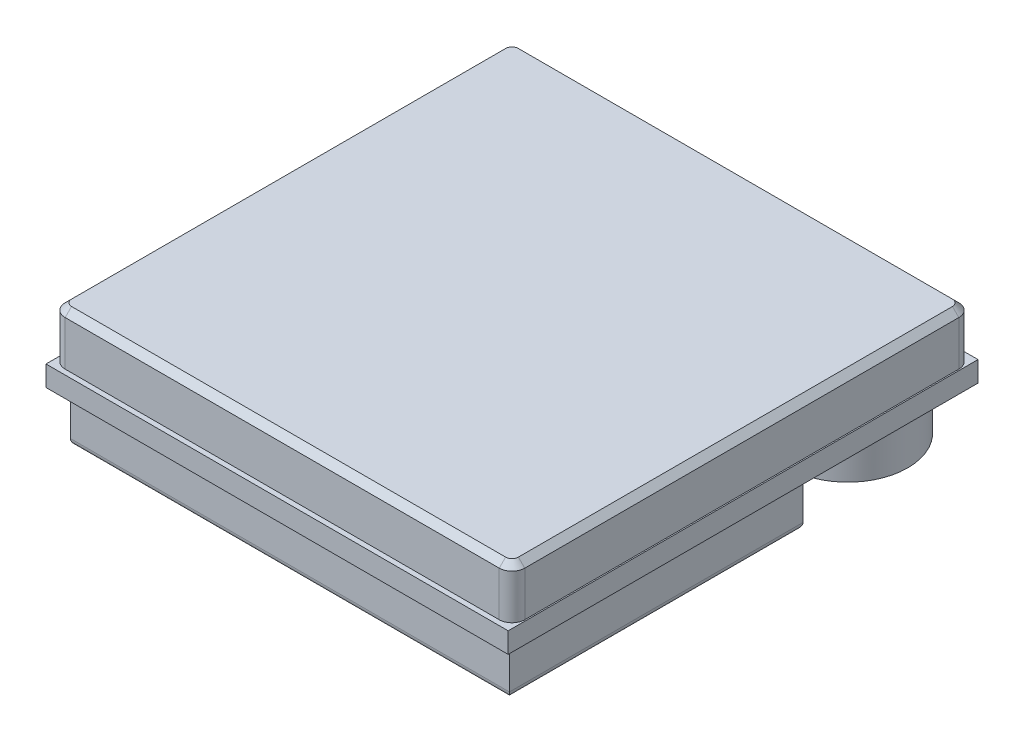
SolidWorks part; units mm, degrees
ref_plane "Front Plane" through (0, 0, 0) normal (0, 0, 1) x (1, 0, 0)
ref_plane "Top Plane" through (0, 0, 0) normal (0, 1, 0) x (1, 0, 0)
ref_plane "Right Plane" through (0, 0, 0) normal (1, 0, 0) x (0, 0, -1)
sketch "Sketch1" plane through (0, 0, 0) normal (0, 1, 0) x (1, 0, 0)
  line L1 (-9.05, 9.2) -> (9.05, 9.2)
  line L2 (-9.05, 9.2) -> (-9.05, -9.2)
  line L3 (-9.05, -9.2) -> (9.05, -9.2)
  line L4 (9.05, 9.2) -> (9.05, -9.2)
  line L5 (-9.05, 9.2) -> (9.05, -9.2) construction
  line L6 (-9.05, -9.2) -> (9.05, 9.2) construction
  point P0 (0, 0)
  dimension "D1" = 18.4
  dimension "D2" = 18.1
extrude "Boss-Extrude1" add sketch "Sketch1" along normal mid plane 0.8
sketch "Sketch2" plane through (0, 0.4, 0) normal (0, 1, 0) x (1, 0, 0)
  line L1 (9, 9) -> (-9, 9)
  line L2 (9, 9) -> (9, -9)
  line L3 (9, -9) -> (-9, -9)
  line L4 (-9, 9) -> (-9, -9)
  line L5 (9, 9) -> (-9, -9) construction
  line L6 (9, -9) -> (-9, 9) construction
  point P0 (0, 0)
  dimension "D1" = 18
extrude "Boss-Extrude2" add sketch "Sketch2" along normal blind 2
sketch "Sketch3" plane through (0, -0.4, 0) normal (0, -1, 0) x (1, 0, 0)
  line L0 (0, 9.2) -> (0, -9.2) construction
  line L1 (-9.05, 9.2) -> (9.05, 9.2) construction
  line L2 (9.05, -9.2) -> (-9.05, -9.2) construction
  line L4 (-3.075, -4.4) -> (3.075, -4.4)
  line L5 (-3.075, -4.4) -> (-3.075, -8.7)
  line L6 (-3.075, -8.7) -> (3.075, -8.7)
  line L7 (3.075, -4.4) -> (3.075, -8.7)
  line L8 (-3.075, -4.4) -> (3.075, -8.7) construction
  line L9 (-3.075, -8.7) -> (3.075, -4.4) construction
  point P6 (0, -6.55)
  dimension "D1" = 6.15
  dimension "D2" = 4.3
  dimension "D3" = 0.5
extrude "Boss-Extrude3" add sketch "Sketch3" along normal blind 3
sketch "Sketch4" plane through (0, 0, -8.7) normal (0, 0, -1) x (-1, 0, 0)
  line L8 (2.575, -0.9) -> (-2.575, -0.9)
  line L9 (-2.575, -0.9) -> (-2.575, -2.9)
  line L10 (-2.575, -2.9) -> (2.575, -2.9)
  line L11 (2.575, -2.9) -> (2.575, -0.9)
  line L12 (2.575, -0.9) -> (-2.575, -0.9)
  line L13 (-2.575, -0.9) -> (-2.575, -2.9)
  line L14 (-2.575, -2.9) -> (2.575, -2.9)
  line L15 (2.575, -2.9) -> (2.575, -0.9)
  dimension "D1" = 0.5
extrude "Cut-Extrude1" cut sketch "Sketch4" against normal blind 3.5
sketch "Sketch5" plane through (0, -0.4, 0) normal (0, -1, 0) x (1, 0, 0)
  line L0 (0, 9.2) -> (0, -9.2) construction
  line L1 (-9.05, 9.2) -> (9.05, 9.2) construction
  line L2 (9.05, -9.2) -> (-9.05, -9.2) construction
  line L4 (-8.6, 8.7) -> (8.6, 8.7)
  line L5 (-8.6, 8.7) -> (-8.6, -2.8)
  line L6 (-8.6, -2.8) -> (8.6, -2.8)
  line L7 (8.6, 8.7) -> (8.6, -2.8)
  line L8 (-8.6, 8.7) -> (8.6, -2.8) construction
  line L9 (-8.6, -2.8) -> (8.6, 8.7) construction
  point P6 (0, 2.95)
  dimension "D1" = 0.5
  dimension "D2" = 17.2
  dimension "D3" = 11.5
extrude "Boss-Extrude4" add sketch "Sketch5" along normal blind 2
fillet "Fillet1" radius 0.25 4 edges at (0, -2.4, -2.8) (-8.6, -2.4, 2.95) (0, -2.4, 8.7) (8.6, -2.4, 2.95)
sketch "Sketch6" plane through (0, -0.4, 0) normal (0, -1, 0) x (1, 0, 0)
  line L9 (8.85, -9) -> (8.85, 9)
  line L10 (8.85, 9) -> (-8.85, 9)
  line L11 (-8.85, 9) -> (-8.85, -9)
  line L12 (-8.85, -9) -> (8.85, -9)
  line L13 (8.85, -9) -> (8.85, 9)
  line L14 (8.85, 9) -> (-8.85, 9)
  line L15 (-8.85, 9) -> (-8.85, -9)
  line L16 (-8.85, -9) -> (8.85, -9)
  circle A0 centre (6.5, -6.65) radius 2.35
  dimension "D2" = 4.7
  dimension "D1" = 0.2
extrude "Boss-Extrude5" add sketch "Sketch6" along normal blind 1.7 contours A0 region at (6.5, -0.4, -6.65)
fillet "Fillet2" radius 0.5 4 edges at (-9, 1.4, -9) (-9, 1.4, 9) (9, 1.4, 9) (9, 1.4, -9)
chamfer "Chamfer1" distance 0.25 angle 45 8 edges at (9, 2.4, 0) (8.8536, 2.4, -8.8536) (8.8536, 2.4, 8.8536) (0, 2.4, -9) (0, 2.4, 9) (-8.8536, 2.4, -8.8536) (-8.8536, 2.4, 8.8536) (-9, 2.4, 0)
